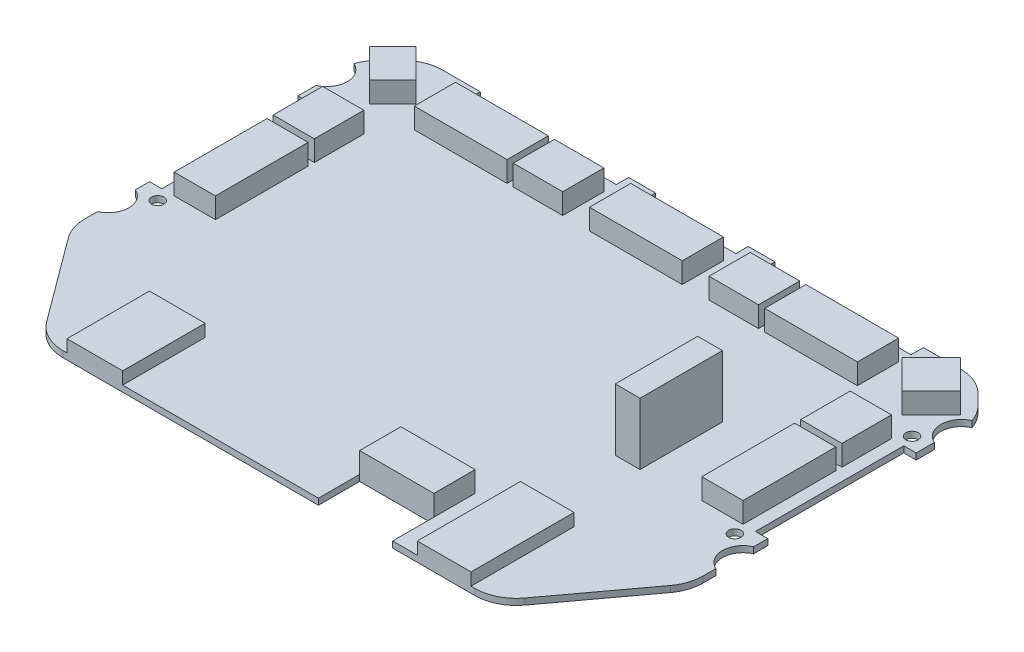
SolidWorks part; units mm, degrees
material "2A12"
ref_plane "前视基准面" through (0, 0, 0) normal (0, 0, 1) x (1, 0, 0)
ref_plane "上视基准面" through (0, 0, 0) normal (0, 1, 0) x (1, 0, 0)
ref_plane "右视基准面" through (0, 0, 0) normal (1, 0, 0) x (0, 0, -1)
sketch "草图2" plane through (0, 0, 0) normal (0, 1, 0) x (1, 0, 0)
  line L0 (237.3542, 167.0401) -> (229.3542, 159.0401)
  line L1 (229.3542, 159.0401) -> (229.3542, 89.0401)
  line L2 (379.3542, 159.0401) -> (379.3542, 89.0401)
  line L3 (249.3542, 62.0401) -> (359.3542, 62.0401)
  line L5 (379.3542, 89.0401) -> (359.3542, 62.0401)
  line L6 (229.3542, 89.0401) -> (249.3542, 62.0401)
  line L7 (316.3542, 62.0401) -> (334.3542, 62.0401)
  line L8 (316.3542, 62.0401) -> (316.3542, 72.0401)
  line L9 (316.3542, 72.0401) -> (334.3542, 72.0401)
  line L10 (334.3542, 62.0401) -> (334.3542, 72.0401)
  line L15 (250.6042, 167.0401) -> (286.6042, 167.0401)
  line L16 (250.6042, 167.0401) -> (250.6042, 164.0401)
  line L17 (250.6042, 164.0401) -> (286.6042, 164.0401)
  line L18 (379.3542, 159.0401) -> (371.3542, 167.0401)
  line L19 (371.3542, 167.0401) -> (237.3542, 167.0401)
  line L20 (286.6042, 167.0401) -> (286.6042, 164.0401)
  line L21 (293.1042, 167.0401) -> (315.6042, 167.0401)
  line L22 (293.1042, 167.0401) -> (293.1042, 164.0401)
  line L23 (293.1042, 164.0401) -> (315.6042, 164.0401)
  line L24 (315.6042, 167.0401) -> (315.6042, 164.0401)
  line L25 (358.1042, 167.0401) -> (322.1042, 167.0401)
  line L26 (358.1042, 167.0401) -> (358.1042, 164.0401)
  line L27 (358.1042, 164.0401) -> (322.1042, 164.0401)
  line L28 (322.1042, 167.0401) -> (322.1042, 164.0401)
  line L29 (229.3542, 144.0401) -> (232.3542, 144.0401)
  line L30 (229.3542, 144.0401) -> (229.3542, 108.0401)
  line L31 (229.3542, 108.0401) -> (232.3542, 108.0401)
  line L32 (232.3542, 144.0401) -> (232.3542, 108.0401)
  line L33 (379.3542, 144.0401) -> (376.3542, 144.0401)
  line L34 (379.3542, 144.0401) -> (379.3542, 108.0401)
  line L35 (379.3542, 108.0401) -> (376.3542, 108.0401)
  line L36 (376.3542, 144.0401) -> (376.3542, 108.0401)
  circle A0 centre (304.3542, 127.0401) radius 85
  circle A1 centre (375.3542, 147.0401) radius 1.5
  circle A2 centre (374.3542, 105.052) radius 1.5
  circle A3 centre (233.3542, 147.0401) radius 1.5
  circle A4 centre (234.3542, 105.052) radius 1.5
  circle A5 centre (381.3542, 153.0401) radius 5
  circle A6 centre (381.3542, 100.0401) radius 5
  circle A7 centre (227.3542, 153.0401) radius 5
  circle A8 centre (227.3542, 100.0401) radius 5
  dimension "D3" = 170
  dimension "D4" = 70
  dimension "D16" = 20
  dimension "D17" = 71
  dimension "D13" = 42
  dimension "D14" = 20
  dimension "D15" = 42
  dimension "D18" = 71
  dimension "D19" = 3
  dimension "D20" = 3
  dimension "D21" = 3
  dimension "D22" = 3
  dimension "D23" = 70
  dimension "D25" = 10
  dimension "D26" = 10
  dimension "D27" = 10
  dimension "D28" = 10
  dimension "D24" = 70
  dimension "D30" = 27
  dimension "D31" = 77
  dimension "D29" = 26
  dimension "D32" = 26
  dimension "D33" = 77
  dimension "D34" = 77
  dimension "D35" = 27
  dimension "D36" = 77
  dimension "D37" = 45
  dimension "D5" = 8
  dimension "D6" = 8
  dimension "D7" = 8
  dimension "D8" = 8
  dimension "D9" = 18
  dimension "D10" = 40
  dimension "D11" = 55
  dimension "D12" = 110
  dimension "D38" = 10
  dimension "D39" = 105
  dimension "D40" = 75
  dimension "D41" = 70
  dimension "D42" = 20
  dimension "D46" = 36
  dimension "D47" = 3
  dimension "D48" = 21.25
  dimension "D49" = 6.5
  dimension "D50" = 3
  dimension "D51" = 22.5
  dimension "D52" = 6.5
  dimension "D53" = 36
  dimension "D54" = 3
  dimension "D55" = 36
  dimension "D56" = 3
  dimension "D57" = 23
  dimension "D58" = 36
  dimension "D59" = 3
  dimension "D60" = 23
extrude "凸台-拉伸1" add sketch "草图2" along normal blind 1.5 contours A8 L1 L6 A0 L3 L8 L9 L10 L5 L2 A6 L35 L36 L33 A5 L18 L19 L26 L27 L28 L24 L23 L22 L20 L17 L16 L0 A7 L29 L32 L31 A4 A3 A2 A1 | A0 L6 L3 | A0 L3 L5 region at (304.0909, 0, -115.281) region at (249.3009, 0, -62.214) region at (359.4074, 0, -62.214)
sketch "草图3" plane through (0, 1.5, 0) normal (0, 1, 0) x (1, 0, 0)
  line L0 (229.3542, 148.4575) -> (229.3542, 144.0401) construction
  line L1 (250.6042, 161.0401) -> (273.1042, 161.0401)
  line L2 (250.6042, 161.0401) -> (250.6042, 151.0401)
  line L3 (250.6042, 151.0401) -> (273.1042, 151.0401)
  line L4 (273.1042, 161.0401) -> (273.1042, 151.0401)
  line L5 (274.6042, 161.0401) -> (286.6042, 161.0401)
  line L6 (274.6042, 161.0401) -> (274.6042, 151.0401)
  line L7 (274.6042, 151.0401) -> (286.6042, 151.0401)
  line L8 (286.6042, 161.0401) -> (286.6042, 151.0401)
  line L9 (293.1042, 161.0401) -> (315.6042, 161.0401)
  line L10 (293.1042, 161.0401) -> (293.1042, 151.0401)
  line L11 (293.1042, 151.0401) -> (315.6042, 151.0401)
  line L12 (315.6042, 161.0401) -> (315.6042, 151.0401)
  line L13 (322.1042, 161.0401) -> (334.1042, 161.0401)
  line L14 (322.1042, 161.0401) -> (322.1042, 151.0401)
  line L15 (322.1042, 151.0401) -> (334.1042, 151.0401)
  line L16 (334.1042, 161.0401) -> (334.1042, 151.0401)
  line L17 (335.6042, 161.0401) -> (358.1042, 161.0401)
  line L18 (335.6042, 161.0401) -> (335.6042, 151.0401)
  line L19 (335.6042, 151.0401) -> (358.1042, 151.0401)
  line L20 (358.1042, 161.0401) -> (358.1042, 151.0401)
  line L21 (363.3542, 144.0401) -> (373.3542, 144.0401)
  line L22 (363.3542, 144.0401) -> (363.3542, 132.0401)
  line L23 (363.3542, 132.0401) -> (373.3542, 132.0401)
  line L24 (373.3542, 144.0401) -> (373.3542, 132.0401)
  line L25 (363.3542, 130.5401) -> (373.3542, 130.5401)
  line L26 (363.3542, 130.5401) -> (363.3542, 108.0401)
  line L27 (363.3542, 108.0401) -> (373.3542, 108.0401)
  line L28 (373.3542, 130.5401) -> (373.3542, 108.0401)
  line L29 (235.3542, 144.0401) -> (245.3542, 144.0401)
  line L30 (235.3542, 144.0401) -> (235.3542, 132.0401)
  line L31 (235.3542, 132.0401) -> (245.3542, 132.0401)
  line L32 (245.3542, 144.0401) -> (245.3542, 132.0401)
  line L33 (235.3542, 130.5401) -> (245.3542, 130.5401)
  line L34 (235.3542, 130.5401) -> (235.3542, 108.0401)
  line L35 (235.3542, 108.0401) -> (245.3542, 108.0401)
  line L36 (245.3542, 130.5401) -> (245.3542, 108.0401)
  line L37 (250.6042, 164.0401) -> (286.6042, 164.0401) construction
  line L38 (293.1042, 164.0401) -> (315.6042, 164.0401) construction
  line L39 (358.1042, 164.0401) -> (322.1042, 164.0401) construction
  line L40 (250.6042, 167.0401) -> (237.3542, 167.0401) construction
  line L41 (232.3542, 144.0401) -> (232.3542, 108.0401) construction
  line L42 (376.3542, 144.0401) -> (376.3542, 108.0401) construction
  line L43 (371.3542, 167.0401) -> (358.1042, 167.0401) construction
  line L44 (232.6471, 158.0903) -> (238.3039, 163.7472)
  line L45 (238.3039, 163.7472) -> (245.375, 156.6761)
  line L46 (245.375, 156.6761) -> (239.7181, 151.0193)
  line L47 (239.7181, 151.0193) -> (232.6471, 158.0903)
  line L48 (237.3542, 167.0401) -> (229.3542, 159.0401) construction
  line L49 (369.6973, 164.4543) -> (376.7684, 157.3832)
  line L50 (376.7684, 157.3832) -> (369.6973, 150.3122)
  line L51 (369.6973, 150.3122) -> (362.6263, 157.3832)
  line L52 (362.6263, 157.3832) -> (369.6973, 164.4543)
  line L53 (379.3542, 159.0401) -> (371.3542, 167.0401) construction
  line L56 (316.3542, 72.0401) -> (334.3542, 72.0401)
  line L57 (316.3542, 72.0401) -> (316.3542, 82.0401)
  line L58 (316.3542, 82.0401) -> (334.3542, 82.0401)
  line L61 (334.3542, 72.0401) -> (334.3542, 82.0401)
  point P50 (364.7292, 167.0401)
  point P55 (233.3542, 163.0401)
  point P66 (375.3542, 163.0401)
  dimension "D1" = 22.5
  dimension "D2" = 12
  dimension "D3" = 1.5
  dimension "D4" = 21.25
  dimension "D5" = 10
  dimension "D6" = 10
  dimension "D7" = 3
  dimension "D8" = 3
  dimension "D9" = 22.5
  dimension "D10" = 6.5
  dimension "D11" = 3
  dimension "D12" = 10
  dimension "D13" = 22.5
  dimension "D14" = 1.5
  dimension "D15" = 12
  dimension "D16" = 6.5
  dimension "D17" = 3
  dimension "D18" = 3
  dimension "D19" = 10
  dimension "D20" = 10
  dimension "D21" = 12
  dimension "D22" = 1.5
  dimension "D23" = 22.5
  dimension "D24" = 23
  dimension "D25" = 10
  dimension "D26" = 3
  dimension "D27" = 10
  dimension "D28" = 3
  dimension "D29" = 12
  dimension "D30" = 10
  dimension "D31" = 3
  dimension "D32" = 1.5
  dimension "D33" = 22.5
  dimension "D34" = 3
  dimension "D35" = 10
  dimension "D36" = 23
  dimension "D37" = 8
  dimension "D38" = 4
  dimension "D39" = 3
  dimension "D40" = 10
  dimension "D41" = 3
  dimension "D42" = 10
  dimension "D43" = 5
  dimension "D44" = 10
  dimension "D45" = 10
  dimension "D46" = 10
extrude "凸台-拉伸2" add sketch "草图3" along normal blind 5
sketch "草图4" plane through (0, 1.5, 0) normal (0, 1, 0) x (1, 0, 0)
  line L0 (371.3542, 167.0401) -> (358.1042, 167.0401) construction
  line L1 (343.3542, 127.0401) -> (349.3542, 127.0401)
  line L2 (343.3542, 127.0401) -> (343.3542, 107.0401)
  line L3 (343.3542, 107.0401) -> (349.3542, 107.0401)
  line L4 (349.3542, 127.0401) -> (349.3542, 107.0401)
  line L5 (379.3542, 148.4575) -> (379.3542, 144.0401) construction
  dimension "D1" = 6
  dimension "D2" = 20
  dimension "D3" = 40
  dimension "D4" = 30
extrude "凸台-拉伸3" add sketch "草图4" along normal blind 15
fillet "圆角1" radius 10 8 edges at (379.3542, 0.75, -89.0401) (379.3542, 0.75, -159.0401) (371.3542, 0.75, -167.0401) (237.3542, 0.75, -167.0401) (229.3542, 0.75, -159.0401) (229.3542, 0.75, -89.0401) (249.3542, 0.75, -62.0401) (359.3542, 0.75, -62.0401)
sketch "草图6" plane through (0, 1.5, 0) normal (0, 1, 0) x (1, 0, 0)
  line L0 (254.3914, 62.0401) -> (316.3542, 62.0401) construction
  line L1 (255.3542, 62.0401) -> (268.8542, 62.0401)
  line L2 (255.3542, 62.0401) -> (255.3542, 82.0401)
  line L3 (255.3542, 82.0401) -> (268.8542, 82.0401)
  line L4 (268.8542, 62.0401) -> (268.8542, 82.0401)
  line L5 (334.3542, 62.0401) -> (354.3169, 62.0401) construction
  line L6 (340.3542, 62.0401) -> (353.3542, 62.0401)
  line L7 (340.3542, 62.0401) -> (340.3542, 87.0401)
  line L8 (340.3542, 87.0401) -> (353.3542, 87.0401)
  line L9 (353.3542, 62.0401) -> (353.3542, 87.0401)
  line L10 (379.3542, 108.0401) -> (379.3542, 104.6227) construction
  line L11 (229.3542, 108.0401) -> (229.3542, 104.6227) construction
  dimension "D1" = 25
  dimension "D2" = 13
  dimension "D3" = 26
  dimension "D4" = 13.5
  dimension "D5" = 26
  dimension "D6" = 20
extrude "凸台-拉伸5" add sketch "草图6" along normal blind 3
